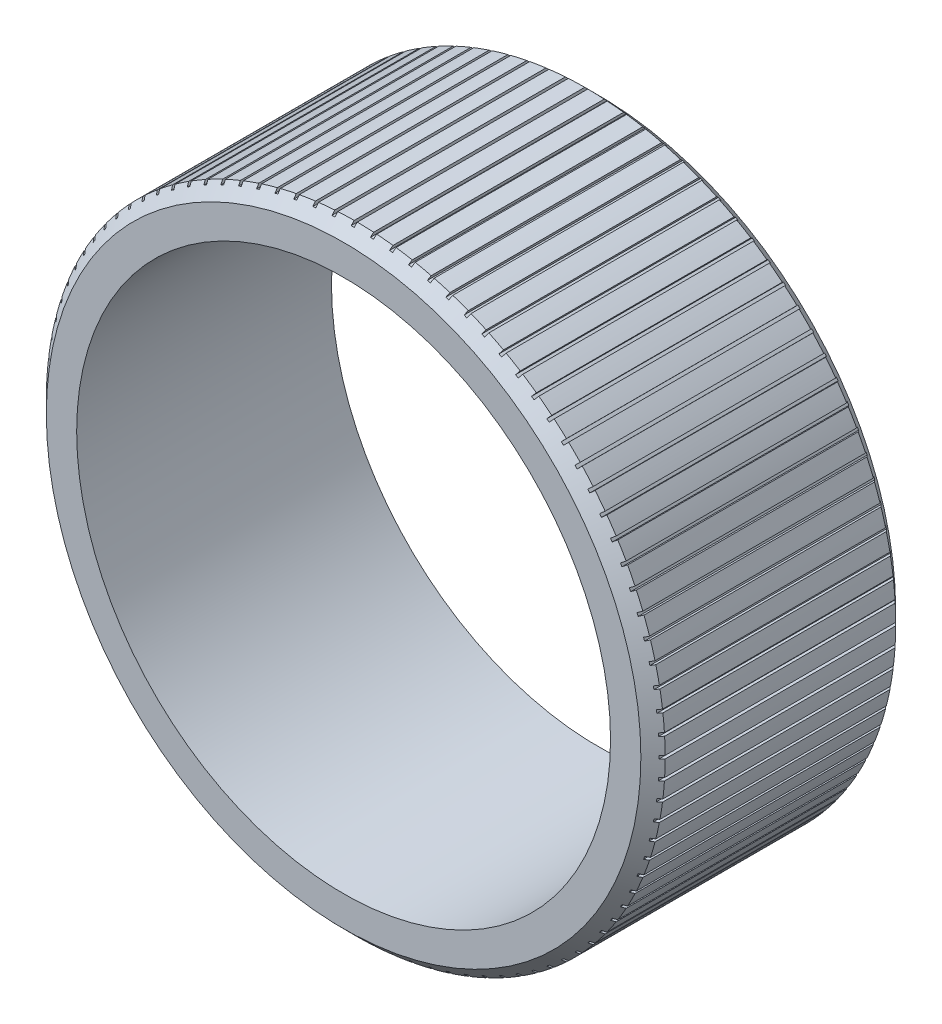
SolidWorks part; units mm, degrees
ref_plane "前视基准面" through (0, 0, 0) normal (0, 0, 1) x (1, 0, 0)
ref_plane "上视基准面" through (0, 0, 0) normal (0, 1, 0) x (1, 0, 0)
ref_plane "右视基准面" through (0, 0, 0) normal (1, 0, 0) x (0, 0, -1)
sketch "草图1" plane through (0, 0, 0) normal (0, 0, 1) x (1, 0, 0)
  circle A0 centre (0, 0) radius 44
  circle A1 centre (0, 0) radius 51
  dimension "D1" = 88
  dimension "D2" = 102
extrude "凸台-拉伸1" add sketch "草图1" along normal blind 42
chamfer "倒角1" distance 2 angle 45 2 edges at (51, 0, 0) (51, 0, 42)
ref_plane "基准面1" through (0, 0, 21) normal (0, 0, 1) x (1, 0, 0)
sketch "草图3" plane through (0, 0, 21) normal (0, 0, 1) x (1, 0, 0)
  line L0 (0, 51) -> (0, -51) construction
  circle A0 centre (0, 0) radius 51 construction
sketch "草图4" plane through (0, 0, 0) normal (0, 0, -1) x (-1, 0, 0)
  line L0 (0, 0) -> (0, 51) construction
  line L1 (-0.25, 51.5006) -> (-0.25, 50.9994) construction
  line L2 (-0.25, 51.5006) -> (0.25, 51.5006) construction
  line L3 (-0.25, 50.9994) -> (-0.25, 50.4994)
  line L4 (-0.25, 50.4994) -> (0, 50.4994) construction
  line L5 (0.25, 50.9994) -> (0.25, 50.4994)
  line L6 (-0.25, 51.5006) -> (0.25, 50.4994) construction
  line L7 (-0.25, 50.4994) -> (0.25, 51.5006) construction
  line L8 (0.25, 51.5006) -> (0.25, 50.9994) construction
  line L9 (0, 50.4994) -> (0.25, 50.4994) construction
  line L10 (3.4518, 50.8831) -> (3.4204, 50.384)
  line L11 (2.9528, 50.9144) -> (2.9214, 50.4154)
  line L12 (6.6399, 50.5659) -> (6.5773, 50.0698)
  line L13 (6.1439, 50.6286) -> (6.0812, 50.1325)
  line L14 (9.8019, 50.0492) -> (9.7082, 49.5581)
  line L15 (9.3108, 50.1429) -> (9.2171, 49.6517)
  line L16 (12.9252, 49.335) -> (12.8008, 48.8507)
  line L17 (12.4409, 49.4593) -> (12.3165, 48.975)
  line L18 (15.9974, 48.426) -> (15.8429, 47.9505)
  line L19 (15.5219, 48.5806) -> (15.3674, 48.105)
  line L20 (19.0066, 47.326) -> (18.8225, 46.8611)
  line L21 (18.5417, 47.5101) -> (18.3576, 47.0452)
  line L22 (21.9407, 46.0392) -> (21.7278, 45.5868)
  line L23 (21.4883, 46.2521) -> (21.2754, 45.7997)
  line L24 (24.7882, 44.5707) -> (24.5473, 44.1325)
  line L25 (24.3501, 44.8115) -> (24.1092, 44.3734)
  line L26 (27.5379, 42.9263) -> (27.27, 42.5041)
  line L27 (27.1158, 43.1942) -> (26.8478, 42.772)
  line L28 (30.1789, 41.1124) -> (29.885, 40.7079)
  line L29 (29.7744, 41.4063) -> (29.4805, 41.0018)
  line L30 (32.7009, 39.1363) -> (32.3821, 38.7511)
  line L31 (32.3156, 39.4551) -> (31.9969, 39.0698)
  line L32 (35.0937, 37.0058) -> (34.7514, 36.6413)
  line L33 (34.7292, 37.3481) -> (34.387, 36.9836)
  line L34 (37.3481, 34.7292) -> (36.9836, 34.387)
  line L35 (37.0058, 35.0937) -> (36.6413, 34.7514)
  line L36 (39.4551, 32.3156) -> (39.0698, 31.9969)
  line L37 (39.1363, 32.7009) -> (38.7511, 32.3821)
  line L38 (41.4063, 29.7744) -> (41.0018, 29.4805)
  line L39 (41.1124, 30.1789) -> (40.7079, 29.885)
  line L40 (43.1942, 27.1158) -> (42.772, 26.8478)
  line L41 (42.9263, 27.5379) -> (42.5041, 27.27)
  line L42 (44.8115, 24.3501) -> (44.3734, 24.1092)
  line L43 (44.5707, 24.7882) -> (44.1325, 24.5473)
  line L44 (46.2521, 21.4883) -> (45.7997, 21.2754)
  line L45 (46.0392, 21.9407) -> (45.5868, 21.7278)
  line L46 (47.5101, 18.5417) -> (47.0452, 18.3576)
  line L47 (47.326, 19.0066) -> (46.8611, 18.8225)
  line L48 (48.5806, 15.5219) -> (48.105, 15.3674)
  line L49 (48.426, 15.9974) -> (47.9505, 15.8429)
  line L50 (49.4593, 12.4409) -> (48.975, 12.3165)
  line L51 (49.335, 12.9252) -> (48.8507, 12.8008)
  line L52 (50.1429, 9.3108) -> (49.6517, 9.2171)
  line L53 (50.0492, 9.8019) -> (49.5581, 9.7082)
  line L54 (50.6286, 6.1439) -> (50.1325, 6.0812)
  line L55 (50.5659, 6.6399) -> (50.0698, 6.5773)
  line L56 (50.9144, 2.9528) -> (50.4154, 2.9214)
  line L57 (50.8831, 3.4518) -> (50.384, 3.4204)
  line L58 (50.9994, -0.25) -> (50.4994, -0.25)
  line L59 (50.9994, 0.25) -> (50.4994, 0.25)
  line L60 (50.8831, -3.4518) -> (50.384, -3.4204)
  line L61 (50.9144, -2.9528) -> (50.4154, -2.9214)
  line L62 (50.5659, -6.6399) -> (50.0698, -6.5773)
  line L63 (50.6286, -6.1439) -> (50.1325, -6.0812)
  line L64 (50.0492, -9.8019) -> (49.5581, -9.7082)
  line L65 (50.1429, -9.3108) -> (49.6517, -9.2171)
  line L66 (49.335, -12.9252) -> (48.8507, -12.8008)
  line L67 (49.4593, -12.4409) -> (48.975, -12.3165)
  line L68 (48.426, -15.9974) -> (47.9505, -15.8429)
  line L69 (48.5806, -15.5219) -> (48.105, -15.3674)
  line L70 (47.326, -19.0066) -> (46.8611, -18.8225)
  line L71 (47.5101, -18.5417) -> (47.0452, -18.3576)
  line L72 (46.0392, -21.9407) -> (45.5868, -21.7278)
  line L73 (46.2521, -21.4883) -> (45.7997, -21.2754)
  line L74 (44.5707, -24.7882) -> (44.1325, -24.5473)
  line L75 (44.8115, -24.3501) -> (44.3734, -24.1092)
  line L76 (42.9263, -27.5379) -> (42.5041, -27.27)
  line L77 (43.1942, -27.1158) -> (42.772, -26.8478)
  line L78 (41.1124, -30.1789) -> (40.7079, -29.885)
  line L79 (41.4063, -29.7744) -> (41.0018, -29.4805)
  line L80 (39.1363, -32.7009) -> (38.7511, -32.3821)
  line L81 (39.4551, -32.3156) -> (39.0698, -31.9969)
  line L82 (37.0058, -35.0937) -> (36.6413, -34.7514)
  line L83 (37.3481, -34.7292) -> (36.9836, -34.387)
  line L84 (34.7292, -37.3481) -> (34.387, -36.9836)
  line L85 (35.0937, -37.0058) -> (34.7514, -36.6413)
  line L86 (32.3156, -39.4551) -> (31.9969, -39.0698)
  line L87 (32.7009, -39.1363) -> (32.3821, -38.7511)
  line L88 (29.7744, -41.4063) -> (29.4805, -41.0018)
  line L89 (30.1789, -41.1124) -> (29.885, -40.7079)
  line L90 (27.1158, -43.1942) -> (26.8478, -42.772)
  line L91 (27.5379, -42.9263) -> (27.27, -42.5041)
  line L92 (24.3501, -44.8115) -> (24.1092, -44.3734)
  line L93 (24.7882, -44.5707) -> (24.5473, -44.1325)
  line L94 (21.4883, -46.2521) -> (21.2754, -45.7997)
  line L95 (21.9407, -46.0392) -> (21.7278, -45.5868)
  line L96 (18.5417, -47.5101) -> (18.3576, -47.0452)
  line L97 (19.0066, -47.326) -> (18.8225, -46.8611)
  line L98 (15.5219, -48.5806) -> (15.3674, -48.105)
  line L99 (15.9974, -48.426) -> (15.8429, -47.9505)
  line L100 (12.4409, -49.4593) -> (12.3165, -48.975)
  line L101 (12.9252, -49.335) -> (12.8008, -48.8507)
  line L102 (9.3108, -50.1429) -> (9.2171, -49.6517)
  line L103 (9.8019, -50.0492) -> (9.7082, -49.5581)
  line L104 (6.1439, -50.6286) -> (6.0812, -50.1325)
  line L105 (6.6399, -50.5659) -> (6.5773, -50.0698)
  line L106 (2.9528, -50.9144) -> (2.9214, -50.4154)
  line L107 (3.4518, -50.8831) -> (3.4204, -50.384)
  line L108 (-0.25, -50.9994) -> (-0.25, -50.4994)
  line L109 (0.25, -50.9994) -> (0.25, -50.4994)
  line L110 (-3.4518, -50.8831) -> (-3.4204, -50.384)
  line L111 (-2.9528, -50.9144) -> (-2.9214, -50.4154)
  line L112 (-6.6399, -50.5659) -> (-6.5773, -50.0698)
  line L113 (-6.1439, -50.6286) -> (-6.0812, -50.1325)
  line L114 (-9.8019, -50.0492) -> (-9.7082, -49.5581)
  line L115 (-9.3108, -50.1429) -> (-9.2171, -49.6517)
  line L116 (-12.9252, -49.335) -> (-12.8008, -48.8507)
  line L117 (-12.4409, -49.4593) -> (-12.3165, -48.975)
  line L118 (-15.9974, -48.426) -> (-15.8429, -47.9505)
  line L119 (-15.5219, -48.5806) -> (-15.3674, -48.105)
  line L120 (-19.0066, -47.326) -> (-18.8225, -46.8611)
  line L121 (-18.5417, -47.5101) -> (-18.3576, -47.0452)
  line L122 (-21.9407, -46.0392) -> (-21.7278, -45.5868)
  line L123 (-21.4883, -46.2521) -> (-21.2754, -45.7997)
  line L124 (-24.7882, -44.5707) -> (-24.5473, -44.1325)
  line L125 (-24.3501, -44.8115) -> (-24.1092, -44.3734)
  line L126 (-27.5379, -42.9263) -> (-27.27, -42.5041)
  line L127 (-27.1158, -43.1942) -> (-26.8478, -42.772)
  line L128 (-30.1789, -41.1124) -> (-29.885, -40.7079)
  line L129 (-29.7744, -41.4063) -> (-29.4805, -41.0018)
  line L130 (-32.7009, -39.1363) -> (-32.3821, -38.7511)
  line L131 (-32.3156, -39.4551) -> (-31.9969, -39.0698)
  line L132 (-35.0937, -37.0058) -> (-34.7514, -36.6413)
  line L133 (-34.7292, -37.3481) -> (-34.387, -36.9836)
  line L134 (-37.3481, -34.7292) -> (-36.9836, -34.387)
  line L135 (-37.0058, -35.0937) -> (-36.6413, -34.7514)
  line L136 (-39.4551, -32.3156) -> (-39.0698, -31.9969)
  line L137 (-39.1363, -32.7009) -> (-38.7511, -32.3821)
  line L138 (-41.4063, -29.7744) -> (-41.0018, -29.4805)
  line L139 (-41.1124, -30.1789) -> (-40.7079, -29.885)
  line L140 (-43.1942, -27.1158) -> (-42.772, -26.8478)
  line L141 (-42.9263, -27.5379) -> (-42.5041, -27.27)
  line L142 (-44.8115, -24.3501) -> (-44.3734, -24.1092)
  line L143 (-44.5707, -24.7882) -> (-44.1325, -24.5473)
  line L144 (-46.2521, -21.4883) -> (-45.7997, -21.2754)
  line L145 (-46.0392, -21.9407) -> (-45.5868, -21.7278)
  line L146 (-47.5101, -18.5417) -> (-47.0452, -18.3576)
  line L147 (-47.326, -19.0066) -> (-46.8611, -18.8225)
  line L148 (-48.5806, -15.5219) -> (-48.105, -15.3674)
  line L149 (-48.426, -15.9974) -> (-47.9505, -15.8429)
  line L150 (-49.4593, -12.4409) -> (-48.975, -12.3165)
  line L151 (-49.335, -12.9252) -> (-48.8507, -12.8008)
  line L152 (-50.1429, -9.3108) -> (-49.6517, -9.2171)
  line L153 (-50.0492, -9.8019) -> (-49.5581, -9.7082)
  line L154 (-50.6286, -6.1439) -> (-50.1325, -6.0812)
  line L155 (-50.5659, -6.6399) -> (-50.0698, -6.5773)
  line L156 (-50.9144, -2.9528) -> (-50.4154, -2.9214)
  line L157 (-50.8831, -3.4518) -> (-50.384, -3.4204)
  line L158 (-50.9994, 0.25) -> (-50.4994, 0.25)
  line L159 (-50.9994, -0.25) -> (-50.4994, -0.25)
  line L160 (-50.8831, 3.4518) -> (-50.384, 3.4204)
  line L161 (-50.9144, 2.9528) -> (-50.4154, 2.9214)
  line L162 (-50.5659, 6.6399) -> (-50.0698, 6.5773)
  line L163 (-50.6286, 6.1439) -> (-50.1325, 6.0812)
  line L164 (-50.0492, 9.8019) -> (-49.5581, 9.7082)
  line L165 (-50.1429, 9.3108) -> (-49.6517, 9.2171)
  line L166 (-49.335, 12.9252) -> (-48.8507, 12.8008)
  line L167 (-49.4593, 12.4409) -> (-48.975, 12.3165)
  line L168 (-48.426, 15.9974) -> (-47.9505, 15.8429)
  line L169 (-48.5806, 15.5219) -> (-48.105, 15.3674)
  line L170 (-47.326, 19.0066) -> (-46.8611, 18.8225)
  line L171 (-47.5101, 18.5417) -> (-47.0452, 18.3576)
  line L172 (-46.0392, 21.9407) -> (-45.5868, 21.7278)
  line L173 (-46.2521, 21.4883) -> (-45.7997, 21.2754)
  line L174 (-44.5707, 24.7882) -> (-44.1325, 24.5473)
  line L175 (-44.8115, 24.3501) -> (-44.3734, 24.1092)
  line L176 (-42.9263, 27.5379) -> (-42.5041, 27.27)
  line L177 (-43.1942, 27.1158) -> (-42.772, 26.8478)
  line L178 (-41.1124, 30.1789) -> (-40.7079, 29.885)
  line L179 (-41.4063, 29.7744) -> (-41.0018, 29.4805)
  line L180 (-39.1363, 32.7009) -> (-38.7511, 32.3821)
  line L181 (-39.4551, 32.3156) -> (-39.0698, 31.9969)
  line L182 (-37.0058, 35.0937) -> (-36.6413, 34.7514)
  line L183 (-37.3481, 34.7292) -> (-36.9836, 34.387)
  line L184 (-34.7292, 37.3481) -> (-34.387, 36.9836)
  line L185 (-35.0937, 37.0058) -> (-34.7514, 36.6413)
  line L186 (-32.3156, 39.4551) -> (-31.9969, 39.0698)
  line L187 (-32.7009, 39.1363) -> (-32.3821, 38.7511)
  line L188 (-29.7744, 41.4063) -> (-29.4805, 41.0018)
  line L189 (-30.1789, 41.1124) -> (-29.885, 40.7079)
  line L190 (-27.1158, 43.1942) -> (-26.8478, 42.772)
  line L191 (-27.5379, 42.9263) -> (-27.27, 42.5041)
  line L192 (-24.3501, 44.8115) -> (-24.1092, 44.3734)
  line L193 (-24.7882, 44.5707) -> (-24.5473, 44.1325)
  line L194 (-21.4883, 46.2521) -> (-21.2754, 45.7997)
  line L195 (-21.9407, 46.0392) -> (-21.7278, 45.5868)
  line L196 (-18.5417, 47.5101) -> (-18.3576, 47.0452)
  line L197 (-19.0066, 47.326) -> (-18.8225, 46.8611)
  line L198 (-15.5219, 48.5806) -> (-15.3674, 48.105)
  line L199 (-15.9974, 48.426) -> (-15.8429, 47.9505)
  line L200 (-12.4409, 49.4593) -> (-12.3165, 48.975)
  line L201 (-12.9252, 49.335) -> (-12.8008, 48.8507)
  line L202 (-9.3108, 50.1429) -> (-9.2171, 49.6517)
  line L203 (-9.8019, 50.0492) -> (-9.7082, 49.5581)
  line L204 (-6.1439, 50.6286) -> (-6.0812, 50.1325)
  line L205 (-6.6399, 50.5659) -> (-6.5773, 50.0698)
  line L206 (-2.9528, 50.9144) -> (-2.9214, 50.4154)
  line L207 (-3.4518, 50.8831) -> (-3.4204, 50.384)
  arc A0 (0.25, 50.9994) -> (-0.25, 50.9994) centre (0, 0) ccw
  circle A1 centre (0, 0) radius 51 construction
  arc A2 (0.25, 50.4994) -> (-0.25, 50.4994) centre (0, 0) ccw
  arc A3 (-0.25, 50.9994) -> (0.25, 50.9994) centre (0, 0) ccw construction
  arc A4 (-0.25, 50.4994) -> (0.25, 50.4994) centre (0, 0) ccw construction
  arc A5 (3.4204, 50.384) -> (2.9214, 50.4154) centre (0, 0) ccw
  arc A6 (3.4518, 50.8831) -> (2.9528, 50.9144) centre (0, 0) ccw
  arc A7 (6.5773, 50.0698) -> (6.0812, 50.1325) centre (0, 0) ccw
  arc A8 (6.6399, 50.5659) -> (6.1439, 50.6286) centre (0, 0) ccw
  arc A9 (9.7082, 49.5581) -> (9.2171, 49.6517) centre (0, 0) ccw
  arc A10 (9.8019, 50.0492) -> (9.3108, 50.1429) centre (0, 0) ccw
  arc A11 (12.8008, 48.8507) -> (12.3165, 48.975) centre (0, 0) ccw
  arc A12 (12.9252, 49.335) -> (12.4409, 49.4593) centre (0, 0) ccw
  arc A13 (15.8429, 47.9505) -> (15.3674, 48.105) centre (0, 0) ccw
  arc A14 (15.9974, 48.426) -> (15.5219, 48.5806) centre (0, 0) ccw
  arc A15 (18.8225, 46.8611) -> (18.3576, 47.0452) centre (0, 0) ccw
  arc A16 (19.0066, 47.326) -> (18.5417, 47.5101) centre (0, 0) ccw
  arc A17 (21.7278, 45.5868) -> (21.2754, 45.7997) centre (0, 0) ccw
  arc A18 (21.9407, 46.0392) -> (21.4883, 46.2521) centre (0, 0) ccw
  arc A19 (24.5473, 44.1325) -> (24.1092, 44.3734) centre (0, 0) ccw
  arc A20 (24.7882, 44.5707) -> (24.3501, 44.8115) centre (0, 0) ccw
  arc A21 (27.27, 42.5041) -> (26.8478, 42.772) centre (0, 0) ccw
  arc A22 (27.5379, 42.9263) -> (27.1158, 43.1942) centre (0, 0) ccw
  arc A23 (29.885, 40.7079) -> (29.4805, 41.0018) centre (0, 0) ccw
  arc A24 (30.1789, 41.1124) -> (29.7744, 41.4063) centre (0, 0) ccw
  arc A25 (32.3821, 38.7511) -> (31.9969, 39.0698) centre (0, 0) ccw
  arc A26 (32.7009, 39.1363) -> (32.3156, 39.4551) centre (0, 0) ccw
  arc A27 (34.7514, 36.6413) -> (34.387, 36.9836) centre (0, 0) ccw
  arc A28 (35.0937, 37.0058) -> (34.7292, 37.3481) centre (0, 0) ccw
  arc A29 (36.9836, 34.387) -> (36.6413, 34.7514) centre (0, 0) ccw
  arc A30 (37.3481, 34.7292) -> (37.0058, 35.0937) centre (0, 0) ccw
  arc A31 (39.0698, 31.9969) -> (38.7511, 32.3821) centre (0, 0) ccw
  arc A32 (39.4551, 32.3156) -> (39.1363, 32.7009) centre (0, 0) ccw
  arc A33 (41.0018, 29.4805) -> (40.7079, 29.885) centre (0, 0) ccw
  arc A34 (41.4063, 29.7744) -> (41.1124, 30.1789) centre (0, 0) ccw
  arc A35 (42.772, 26.8478) -> (42.5041, 27.27) centre (0, 0) ccw
  arc A36 (43.1942, 27.1158) -> (42.9263, 27.5379) centre (0, 0) ccw
  arc A37 (44.3734, 24.1092) -> (44.1325, 24.5473) centre (0, 0) ccw
  arc A38 (44.8115, 24.3501) -> (44.5707, 24.7882) centre (0, 0) ccw
  arc A39 (45.7997, 21.2754) -> (45.5868, 21.7278) centre (0, 0) ccw
  arc A40 (46.2521, 21.4883) -> (46.0392, 21.9407) centre (0, 0) ccw
  arc A41 (47.0452, 18.3576) -> (46.8611, 18.8225) centre (0, 0) ccw
  arc A42 (47.5101, 18.5417) -> (47.326, 19.0066) centre (0, 0) ccw
  arc A43 (48.105, 15.3674) -> (47.9505, 15.8429) centre (0, 0) ccw
  arc A44 (48.5806, 15.5219) -> (48.426, 15.9974) centre (0, 0) ccw
  arc A45 (48.975, 12.3165) -> (48.8507, 12.8008) centre (0, 0) ccw
  arc A46 (49.4593, 12.4409) -> (49.335, 12.9252) centre (0, 0) ccw
  arc A47 (49.6517, 9.2171) -> (49.5581, 9.7082) centre (0, 0) ccw
  arc A48 (50.1429, 9.3108) -> (50.0492, 9.8019) centre (0, 0) ccw
  arc A49 (50.1325, 6.0812) -> (50.0698, 6.5773) centre (0, 0) ccw
  arc A50 (50.6286, 6.1439) -> (50.5659, 6.6399) centre (0, 0) ccw
  arc A51 (50.4154, 2.9214) -> (50.384, 3.4204) centre (0, 0) ccw
  arc A52 (50.9144, 2.9528) -> (50.8831, 3.4518) centre (0, 0) ccw
  arc A53 (50.4994, -0.25) -> (50.4994, 0.25) centre (0, 0) ccw
  arc A54 (50.9994, -0.25) -> (50.9994, 0.25) centre (0, 0) ccw
  arc A55 (50.384, -3.4204) -> (50.4154, -2.9214) centre (0, 0) ccw
  arc A56 (50.8831, -3.4518) -> (50.9144, -2.9528) centre (0, 0) ccw
  arc A57 (50.0698, -6.5773) -> (50.1325, -6.0812) centre (0, 0) ccw
  arc A58 (50.5659, -6.6399) -> (50.6286, -6.1439) centre (0, 0) ccw
  arc A59 (49.5581, -9.7082) -> (49.6517, -9.2171) centre (0, 0) ccw
  arc A60 (50.0492, -9.8019) -> (50.1429, -9.3108) centre (0, 0) ccw
  arc A61 (48.8507, -12.8008) -> (48.975, -12.3165) centre (0, 0) ccw
  arc A62 (49.335, -12.9252) -> (49.4593, -12.4409) centre (0, 0) ccw
  arc A63 (47.9505, -15.8429) -> (48.105, -15.3674) centre (0, 0) ccw
  arc A64 (48.426, -15.9974) -> (48.5806, -15.5219) centre (0, 0) ccw
  arc A65 (46.8611, -18.8225) -> (47.0452, -18.3576) centre (0, 0) ccw
  arc A66 (47.326, -19.0066) -> (47.5101, -18.5417) centre (0, 0) ccw
  arc A67 (45.5868, -21.7278) -> (45.7997, -21.2754) centre (0, 0) ccw
  arc A68 (46.0392, -21.9407) -> (46.2521, -21.4883) centre (0, 0) ccw
  arc A69 (44.1325, -24.5473) -> (44.3734, -24.1092) centre (0, 0) ccw
  arc A70 (44.5707, -24.7882) -> (44.8115, -24.3501) centre (0, 0) ccw
  arc A71 (42.5041, -27.27) -> (42.772, -26.8478) centre (0, 0) ccw
  arc A72 (42.9263, -27.5379) -> (43.1942, -27.1158) centre (0, 0) ccw
  arc A73 (40.7079, -29.885) -> (41.0018, -29.4805) centre (0, 0) ccw
  arc A74 (41.1124, -30.1789) -> (41.4063, -29.7744) centre (0, 0) ccw
  arc A75 (38.7511, -32.3821) -> (39.0698, -31.9969) centre (0, 0) ccw
  arc A76 (39.1363, -32.7009) -> (39.4551, -32.3156) centre (0, 0) ccw
  arc A77 (36.6413, -34.7514) -> (36.9836, -34.387) centre (0, 0) ccw
  arc A78 (37.0058, -35.0937) -> (37.3481, -34.7292) centre (0, 0) ccw
  arc A79 (34.387, -36.9836) -> (34.7514, -36.6413) centre (0, 0) ccw
  arc A80 (34.7292, -37.3481) -> (35.0937, -37.0058) centre (0, 0) ccw
  arc A81 (31.9969, -39.0698) -> (32.3821, -38.7511) centre (0, 0) ccw
  arc A82 (32.3156, -39.4551) -> (32.7009, -39.1363) centre (0, 0) ccw
  arc A83 (29.4805, -41.0018) -> (29.885, -40.7079) centre (0, 0) ccw
  arc A84 (29.7744, -41.4063) -> (30.1789, -41.1124) centre (0, 0) ccw
  arc A85 (26.8478, -42.772) -> (27.27, -42.5041) centre (0, 0) ccw
  arc A86 (27.1158, -43.1942) -> (27.5379, -42.9263) centre (0, 0) ccw
  arc A87 (24.1092, -44.3734) -> (24.5473, -44.1325) centre (0, 0) ccw
  arc A88 (24.3501, -44.8115) -> (24.7882, -44.5707) centre (0, 0) ccw
  arc A89 (21.2754, -45.7997) -> (21.7278, -45.5868) centre (0, 0) ccw
  arc A90 (21.4883, -46.2521) -> (21.9407, -46.0392) centre (0, 0) ccw
  arc A91 (18.3576, -47.0452) -> (18.8225, -46.8611) centre (0, 0) ccw
  arc A92 (18.5417, -47.5101) -> (19.0066, -47.326) centre (0, 0) ccw
  arc A93 (15.3674, -48.105) -> (15.8429, -47.9505) centre (0, 0) ccw
  arc A94 (15.5219, -48.5806) -> (15.9974, -48.426) centre (0, 0) ccw
  arc A95 (12.3165, -48.975) -> (12.8008, -48.8507) centre (0, 0) ccw
  arc A96 (12.4409, -49.4593) -> (12.9252, -49.335) centre (0, 0) ccw
  arc A97 (9.2171, -49.6517) -> (9.7082, -49.5581) centre (0, 0) ccw
  arc A98 (9.3108, -50.1429) -> (9.8019, -50.0492) centre (0, 0) ccw
  arc A99 (6.0812, -50.1325) -> (6.5773, -50.0698) centre (0, 0) ccw
  arc A100 (6.1439, -50.6286) -> (6.6399, -50.5659) centre (0, 0) ccw
  arc A101 (2.9214, -50.4154) -> (3.4204, -50.384) centre (0, 0) ccw
  arc A102 (2.9528, -50.9144) -> (3.4518, -50.8831) centre (0, 0) ccw
  arc A103 (-0.25, -50.4994) -> (0.25, -50.4994) centre (0, 0) ccw
  arc A104 (-0.25, -50.9994) -> (0.25, -50.9994) centre (0, 0) ccw
  arc A105 (-3.4204, -50.384) -> (-2.9214, -50.4154) centre (0, 0) ccw
  arc A106 (-3.4518, -50.8831) -> (-2.9528, -50.9144) centre (0, 0) ccw
  arc A107 (-6.5773, -50.0698) -> (-6.0812, -50.1325) centre (0, 0) ccw
  arc A108 (-6.6399, -50.5659) -> (-6.1439, -50.6286) centre (0, 0) ccw
  arc A109 (-9.7082, -49.5581) -> (-9.2171, -49.6517) centre (0, 0) ccw
  arc A110 (-9.8019, -50.0492) -> (-9.3108, -50.1429) centre (0, 0) ccw
  arc A111 (-12.8008, -48.8507) -> (-12.3165, -48.975) centre (0, 0) ccw
  arc A112 (-12.9252, -49.335) -> (-12.4409, -49.4593) centre (0, 0) ccw
  arc A113 (-15.8429, -47.9505) -> (-15.3674, -48.105) centre (0, 0) ccw
  arc A114 (-15.9974, -48.426) -> (-15.5219, -48.5806) centre (0, 0) ccw
  arc A115 (-18.8225, -46.8611) -> (-18.3576, -47.0452) centre (0, 0) ccw
  arc A116 (-19.0066, -47.326) -> (-18.5417, -47.5101) centre (0, 0) ccw
  arc A117 (-21.7278, -45.5868) -> (-21.2754, -45.7997) centre (0, 0) ccw
  arc A118 (-21.9407, -46.0392) -> (-21.4883, -46.2521) centre (0, 0) ccw
  arc A119 (-24.5473, -44.1325) -> (-24.1092, -44.3734) centre (0, 0) ccw
  arc A120 (-24.7882, -44.5707) -> (-24.3501, -44.8115) centre (0, 0) ccw
  arc A121 (-27.27, -42.5041) -> (-26.8478, -42.772) centre (0, 0) ccw
  arc A122 (-27.5379, -42.9263) -> (-27.1158, -43.1942) centre (0, 0) ccw
  arc A123 (-29.885, -40.7079) -> (-29.4805, -41.0018) centre (0, 0) ccw
  arc A124 (-30.1789, -41.1124) -> (-29.7744, -41.4063) centre (0, 0) ccw
  arc A125 (-32.3821, -38.7511) -> (-31.9969, -39.0698) centre (0, 0) ccw
  arc A126 (-32.7009, -39.1363) -> (-32.3156, -39.4551) centre (0, 0) ccw
  arc A127 (-34.7514, -36.6413) -> (-34.387, -36.9836) centre (0, 0) ccw
  arc A128 (-35.0937, -37.0058) -> (-34.7292, -37.3481) centre (0, 0) ccw
  arc A129 (-36.9836, -34.387) -> (-36.6413, -34.7514) centre (0, 0) ccw
  arc A130 (-37.3481, -34.7292) -> (-37.0058, -35.0937) centre (0, 0) ccw
  arc A131 (-39.0698, -31.9969) -> (-38.7511, -32.3821) centre (0, 0) ccw
  arc A132 (-39.4551, -32.3156) -> (-39.1363, -32.7009) centre (0, 0) ccw
  arc A133 (-41.0018, -29.4805) -> (-40.7079, -29.885) centre (0, 0) ccw
  arc A134 (-41.4063, -29.7744) -> (-41.1124, -30.1789) centre (0, 0) ccw
  arc A135 (-42.772, -26.8478) -> (-42.5041, -27.27) centre (0, 0) ccw
  arc A136 (-43.1942, -27.1158) -> (-42.9263, -27.5379) centre (0, 0) ccw
  arc A137 (-44.3734, -24.1092) -> (-44.1325, -24.5473) centre (0, 0) ccw
  arc A138 (-44.8115, -24.3501) -> (-44.5707, -24.7882) centre (0, 0) ccw
  arc A139 (-45.7997, -21.2754) -> (-45.5868, -21.7278) centre (0, 0) ccw
  arc A140 (-46.2521, -21.4883) -> (-46.0392, -21.9407) centre (0, 0) ccw
  arc A141 (-47.0452, -18.3576) -> (-46.8611, -18.8225) centre (0, 0) ccw
  arc A142 (-47.5101, -18.5417) -> (-47.326, -19.0066) centre (0, 0) ccw
  arc A143 (-48.105, -15.3674) -> (-47.9505, -15.8429) centre (0, 0) ccw
  arc A144 (-48.5806, -15.5219) -> (-48.426, -15.9974) centre (0, 0) ccw
  arc A145 (-48.975, -12.3165) -> (-48.8507, -12.8008) centre (0, 0) ccw
  arc A146 (-49.4593, -12.4409) -> (-49.335, -12.9252) centre (0, 0) ccw
  arc A147 (-49.6517, -9.2171) -> (-49.5581, -9.7082) centre (0, 0) ccw
  arc A148 (-50.1429, -9.3108) -> (-50.0492, -9.8019) centre (0, 0) ccw
  arc A149 (-50.1325, -6.0812) -> (-50.0698, -6.5773) centre (0, 0) ccw
  arc A150 (-50.6286, -6.1439) -> (-50.5659, -6.6399) centre (0, 0) ccw
  arc A151 (-50.4154, -2.9214) -> (-50.384, -3.4204) centre (0, 0) ccw
  arc A152 (-50.9144, -2.9528) -> (-50.8831, -3.4518) centre (0, 0) ccw
  arc A153 (-50.4994, 0.25) -> (-50.4994, -0.25) centre (0, 0) ccw
  arc A154 (-50.9994, 0.25) -> (-50.9994, -0.25) centre (0, 0) ccw
  arc A155 (-50.384, 3.4204) -> (-50.4154, 2.9214) centre (0, 0) ccw
  arc A156 (-50.8831, 3.4518) -> (-50.9144, 2.9528) centre (0, 0) ccw
  arc A157 (-50.0698, 6.5773) -> (-50.1325, 6.0812) centre (0, 0) ccw
  arc A158 (-50.5659, 6.6399) -> (-50.6286, 6.1439) centre (0, 0) ccw
  arc A159 (-49.5581, 9.7082) -> (-49.6517, 9.2171) centre (0, 0) ccw
  arc A160 (-50.0492, 9.8019) -> (-50.1429, 9.3108) centre (0, 0) ccw
  arc A161 (-48.8507, 12.8008) -> (-48.975, 12.3165) centre (0, 0) ccw
  arc A162 (-49.335, 12.9252) -> (-49.4593, 12.4409) centre (0, 0) ccw
  arc A163 (-47.9505, 15.8429) -> (-48.105, 15.3674) centre (0, 0) ccw
  arc A164 (-48.426, 15.9974) -> (-48.5806, 15.5219) centre (0, 0) ccw
  arc A165 (-46.8611, 18.8225) -> (-47.0452, 18.3576) centre (0, 0) ccw
  arc A166 (-47.326, 19.0066) -> (-47.5101, 18.5417) centre (0, 0) ccw
  arc A167 (-45.5868, 21.7278) -> (-45.7997, 21.2754) centre (0, 0) ccw
  arc A168 (-46.0392, 21.9407) -> (-46.2521, 21.4883) centre (0, 0) ccw
  arc A169 (-44.1325, 24.5473) -> (-44.3734, 24.1092) centre (0, 0) ccw
  arc A170 (-44.5707, 24.7882) -> (-44.8115, 24.3501) centre (0, 0) ccw
  arc A171 (-42.5041, 27.27) -> (-42.772, 26.8478) centre (0, 0) ccw
  arc A172 (-42.9263, 27.5379) -> (-43.1942, 27.1158) centre (0, 0) ccw
  arc A173 (-40.7079, 29.885) -> (-41.0018, 29.4805) centre (0, 0) ccw
  arc A174 (-41.1124, 30.1789) -> (-41.4063, 29.7744) centre (0, 0) ccw
  arc A175 (-38.7511, 32.3821) -> (-39.0698, 31.9969) centre (0, 0) ccw
  arc A176 (-39.1363, 32.7009) -> (-39.4551, 32.3156) centre (0, 0) ccw
  arc A177 (-36.6413, 34.7514) -> (-36.9836, 34.387) centre (0, 0) ccw
  arc A178 (-37.0058, 35.0937) -> (-37.3481, 34.7292) centre (0, 0) ccw
  arc A179 (-34.387, 36.9836) -> (-34.7514, 36.6413) centre (0, 0) ccw
  arc A180 (-34.7292, 37.3481) -> (-35.0937, 37.0058) centre (0, 0) ccw
  arc A181 (-31.9969, 39.0698) -> (-32.3821, 38.7511) centre (0, 0) ccw
  arc A182 (-32.3156, 39.4551) -> (-32.7009, 39.1363) centre (0, 0) ccw
  arc A183 (-29.4805, 41.0018) -> (-29.885, 40.7079) centre (0, 0) ccw
  arc A184 (-29.7744, 41.4063) -> (-30.1789, 41.1124) centre (0, 0) ccw
  arc A185 (-26.8478, 42.772) -> (-27.27, 42.5041) centre (0, 0) ccw
  arc A186 (-27.1158, 43.1942) -> (-27.5379, 42.9263) centre (0, 0) ccw
  arc A187 (-24.1092, 44.3734) -> (-24.5473, 44.1325) centre (0, 0) ccw
  arc A188 (-24.3501, 44.8115) -> (-24.7882, 44.5707) centre (0, 0) ccw
  arc A189 (-21.2754, 45.7997) -> (-21.7278, 45.5868) centre (0, 0) ccw
  arc A190 (-21.4883, 46.2521) -> (-21.9407, 46.0392) centre (0, 0) ccw
  arc A191 (-18.3576, 47.0452) -> (-18.8225, 46.8611) centre (0, 0) ccw
  arc A192 (-18.5417, 47.5101) -> (-19.0066, 47.326) centre (0, 0) ccw
  arc A193 (-15.3674, 48.105) -> (-15.8429, 47.9505) centre (0, 0) ccw
  arc A194 (-15.5219, 48.5806) -> (-15.9974, 48.426) centre (0, 0) ccw
  arc A195 (-12.3165, 48.975) -> (-12.8008, 48.8507) centre (0, 0) ccw
  arc A196 (-12.4409, 49.4593) -> (-12.9252, 49.335) centre (0, 0) ccw
  arc A197 (-9.2171, 49.6517) -> (-9.7082, 49.5581) centre (0, 0) ccw
  arc A198 (-9.3108, 50.1429) -> (-9.8019, 50.0492) centre (0, 0) ccw
  arc A199 (-6.0812, 50.1325) -> (-6.5773, 50.0698) centre (0, 0) ccw
  arc A200 (-6.1439, 50.6286) -> (-6.6399, 50.5659) centre (0, 0) ccw
  arc A201 (-2.9214, 50.4154) -> (-3.4204, 50.384) centre (0, 0) ccw
  arc A202 (-2.9528, 50.9144) -> (-3.4518, 50.8831) centre (0, 0) ccw
  point P411 (0, 0)
  dimension "D1" = 0.5
  dimension "0.5" = 0.5
  dimension "D2" = 100
extrude "切除-拉伸1" cut sketch "草图4" against normal up to next
